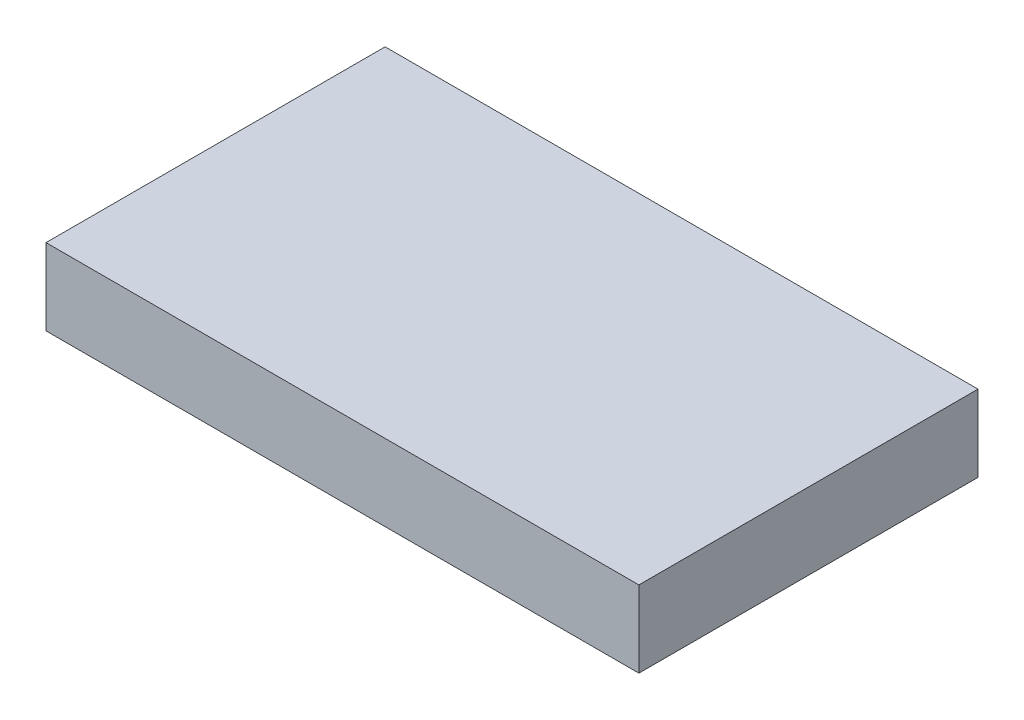
SolidWorks part; units mm, degrees
ref_plane "前视基准面" through (0, 0, 0) normal (0, 0, 1) x (1, 0, 0)
ref_plane "上视基准面" through (0, 0, 0) normal (0, 1, 0) x (1, 0, 0)
ref_plane "右视基准面" through (0, 0, 0) normal (1, 0, 0) x (0, 0, -1)
sketch "草图1" plane through (0, 0, 0) normal (0, 1, 0) x (1, 0, 0)
  line L1 (0, 0) -> (77.5667, 0)
  line L2 (0, 0) -> (0, -44.3647)
  line L3 (0, -44.3647) -> (77.5667, -44.3647)
  line L4 (77.5667, 0) -> (77.5667, -44.3647)
extrude "凸台-拉伸1" add sketch "草图1" along normal blind 10
